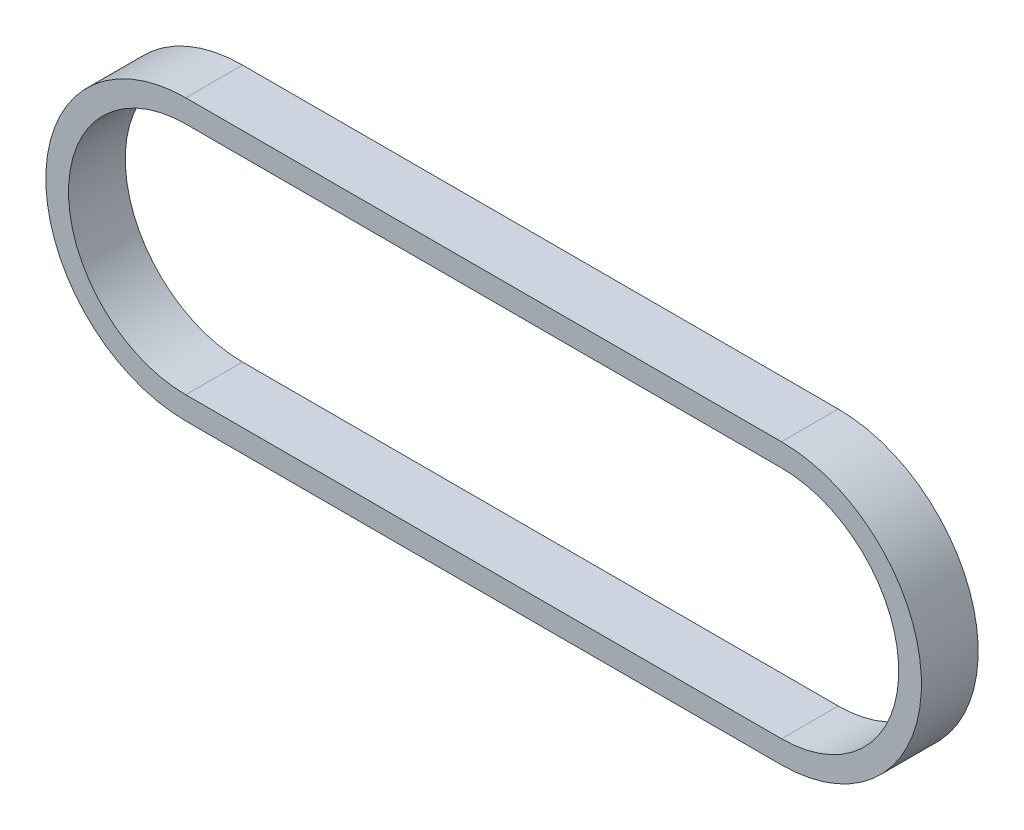
SolidWorks part; units mm, degrees
ref_plane "Plan de face" through (0, 0, 0) normal (0, 0, 1) x (1, 0, 0)
ref_plane "Plan de dessus" through (0, 0, 0) normal (0, 1, 0) x (1, 0, 0)
ref_plane "Plan de droite" through (0, 0, 0) normal (1, 0, 0) x (0, 0, -1)
sketch "Esquisse1" plane through (0, 0, 0) normal (0, 0, 1) x (1, 0, 0)
  line L0 (0, 0) -> (63, 0) construction
  line L1 (0, 12.4) -> (63, 12.4)
  line L2 (0, -12.4) -> (63, -12.4)
  line L3 (0, 0) -> (63, 0) construction
  line L4 (0, 14.8) -> (63, 14.8)
  line L5 (0, -14.8) -> (63, -14.8)
  arc A0 (0, 12.4) -> (0, -12.4) centre (0, 0) ccw
  arc A1 (63, -12.4) -> (63, 12.4) centre (63, 0) ccw
  arc A2 (0, 14.8) -> (0, -14.8) centre (0, 0) ccw
  arc A3 (63, -14.8) -> (63, 14.8) centre (63, 0) ccw
  point P3 (31.5, 0)
  point P10 (31.5, 0)
  dimension "D3" = 12.4
  dimension "D1" = 63
  dimension "D2" = 2.4
extrude "Boss.-Extru.1" add sketch "Esquisse1" along normal blind 6
